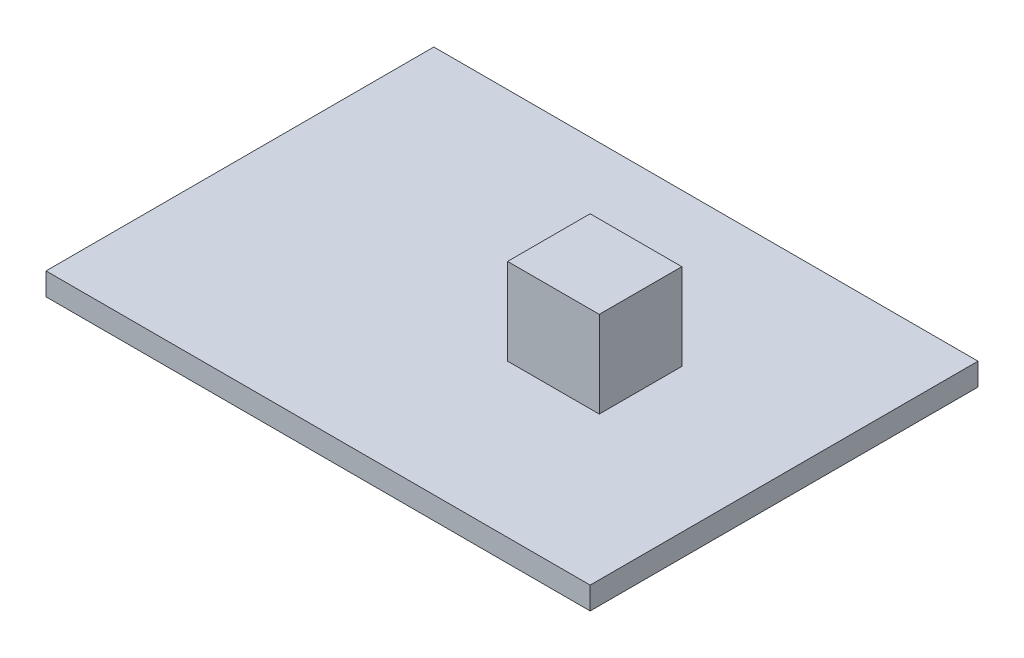
SolidWorks part; units mm, degrees
ref_plane "Front Plane" through (0, 0, 0) normal (0, 0, 1) x (1, 0, 0)
ref_plane "Top Plane" through (0, 0, 0) normal (0, 1, 0) x (1, 0, 0)
ref_plane "Right Plane" through (0, 0, 0) normal (1, 0, 0) x (0, 0, -1)
sketch "Sketch1" plane through (0, 0, 0) normal (0, 1, 0) x (1, 0, 0)
  line L1 (-35.9213, 22.9) -> (27.0787, 22.9)
  line L2 (-35.9213, 22.9) -> (-35.9213, -22)
  line L3 (-35.9213, -22) -> (27.0787, -22)
  line L4 (27.0787, 22.9) -> (27.0787, -22)
  dimension "D1" = 44.9
  dimension "D2" = 63
extrude "Boss-Extrude1" add sketch "Sketch1" along normal blind 2.6
sketch "Sketch3" plane through (0, 2.6, 0) normal (0, 1, 0) x (1, 0, 0)
  line L0 (-56.3565, 0.45) -> (51.0953, 0.45) construction
  line L1 (-0.154, 5.2295) -> (10.4597, 5.2295)
  line L2 (-0.154, 5.2295) -> (-0.154, -4.3295)
  line L3 (-0.154, -4.3295) -> (10.4597, -4.3295)
  line L4 (10.4597, 5.2295) -> (10.4597, -4.3295)
  line L5 (27.0787, 22.9) -> (-35.9213, 22.9) construction
  line L6 (-35.9213, -22) -> (27.0787, -22) construction
extrude "Boss-Extrude2" add sketch "Sketch3" along normal blind 10
